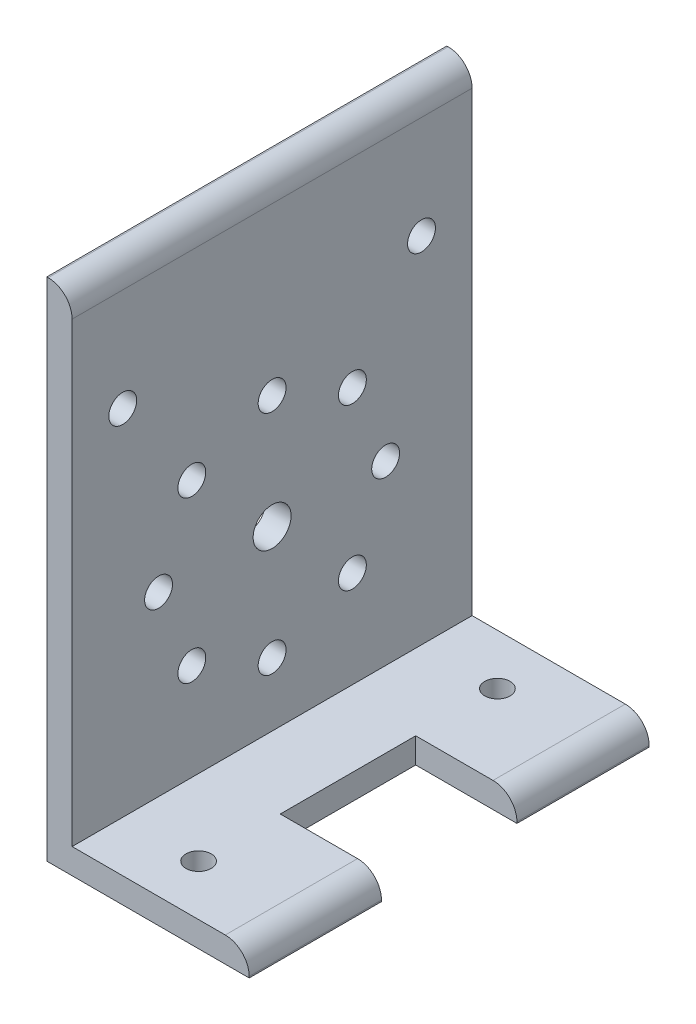
SolidWorks part; units mm, degrees
ref_plane "Front Plane" through (0, 0, 0) normal (0, 0, 1) x (1, 0, 0)
ref_plane "Top Plane" through (0, 0, 0) normal (0, 1, 0) x (1, 0, 0)
ref_plane "Right Plane" through (0, 0, 0) normal (1, 0, 0) x (0, 0, -1)
sketch "Sketch1" plane through (0, 0, 0) normal (0, 0, 1) x (1, 0, 0)
  line L0 (12.35, 6.35) -> (6.35, 6.35)
  line L1 (0, 0) -> (6.35, 0)
  line L2 (0, 0) -> (0, 127)
  line L3 (0, 127) -> (0.35, 127)
  line L4 (6.35, 37.75) -> (6.35, 121)
  line L5 (0, 0) -> (50.8, 0)
  line L6 (0, 0) -> (0, 6.35)
  line L7 (12.35, 6.35) -> (44.8, 6.35)
  line L8 (50.8, 0) -> (50.8, 0.35)
  line L9 (6.35, 6.35) -> (6.35, 37.75)
  arc A0 (44.8, 6.35) -> (50.8, 0.35) centre (44.8, 0.35) cw
  arc A1 (0.35, 127) -> (6.35, 121) centre (0.35, 121) cw
  point P10 (50.8, 6.35)
  point P13 (6.35, 127)
  dimension "D5" = 6
  dimension "D1" = 127
  dimension "D2" = 50.8
  dimension "D3" = 6.35
  dimension "D4" = 6.35
extrude "Boss-Extrude1" add sketch "Sketch1" along normal blind 100.4 contours L7 L4 A1 L3 L2 L1 L5 L8 A0 region at (28.575, 4.9822, 0)
sketch "Sketch2" plane through (0, 0, 0) normal (-1, 0, 0) x (0, 0, 1)
  line L0 (50.2, 0) -> (50.2, 127) construction
  line L1 (100.4, 0) -> (0, 0) construction
  line L2 (100.4, 127) -> (0, 127) construction
  line L3 (100.4, 50.8) -> (0, 50.8) construction
  line L4 (100.4, 0) -> (100.4, 127) construction
  line L5 (0, 0) -> (0, 127) construction
  circle A0 centre (50.2, 50.8) radius 28.5 construction
  circle A9 centre (50.2, 50.8) radius 4.7625
  circle A10 centre (50.2, 79.3) radius 3.5
  circle A18 centre (70.3525, 70.9525) radius 3.5
  circle A19 centre (78.7, 50.8) radius 3.5
  circle A20 centre (70.3525, 30.6475) radius 3.5
  circle A21 centre (50.2, 22.3) radius 3.5
  circle A22 centre (30.0475, 30.6475) radius 3.5
  circle A23 centre (21.7, 50.8) radius 3.5
  circle A24 centre (30.0475, 70.9525) radius 3.5
  dimension "D1" = 57
  dimension "D2" = 8
  dimension "D4" = 9.525
  dimension "D5" = 50.8
extrude "Cut-Extrude1" cut sketch "Sketch2" against normal through all
sketch "Sketch3" plane through (0, 6.35, 0) normal (0, 1, 0) x (1, 0, 0)
  line L0 (25.4, 0) -> (25.4, -100.4) construction
  line L1 (6.35, 0) -> (44.8, 0) construction
  line L2 (6.35, -100.4) -> (44.8, -100.4) construction
  line L3 (0, -100.4) -> (0, 0) construction
  circle A0 centre (25.4, -12.7) radius 3.175
  circle A2 centre (25.4, -87.7) radius 3.175
  dimension "D2" = 6.35
  dimension "D3" = 12.7
  dimension "D5" = 6.35
  dimension "D6" = 12.7
  dimension "D1" = 25.4
extrude "Cut-Extrude2" cut sketch "Sketch3" against normal through all
ref_plane "Width Centerline Plane" through (0, 0, 50.2) normal (0, 0, 1) x (1, 0, 0)
sketch "Sketch4" plane through (0, 6.35, 0) normal (0, 1, 0) x (1, 0, 0)
  line L0 (44.8, 0) -> (44.8, -100.4) construction
  line L5 (50.8, -100.4) -> (50.8, 0) construction
  line L6 (0, -50.2) -> (25.4, -50.2) construction
  line L9 (50.8, -50.2) -> (50.8, -33.2)
  line L10 (50.8, -33.2) -> (25.4, -33.2)
  line L11 (25.4, -50.2) -> (25.4, -33.2)
  line L13 (25.4, -50.2) -> (25.4, -67.2)
  line L14 (25.4, -67.2) -> (50.8, -67.2)
  line L15 (50.8, -50.2) -> (50.8, -67.2)
  point P8 (44.8, -50.2)
  dimension "D1" = 25.4
  dimension "D2" = 17
  dimension "D3" = 17
extrude "Cut-Extrude3" cut sketch "Sketch4" against normal through all
sketch "Sketch5" plane through (6.35, 0, 0) normal (1, 0, 0) x (0, 0, -1)
  line L0 (-50.2, 121) -> (-50.2, 6.35) construction
  line L1 (-100.4, 121) -> (0, 121) construction
  line L3 (-100.4, 6.35) -> (-100.4, 121) construction
  line L4 (-100.4, 6.35) -> (0, 6.35) construction
  circle A0 centre (-87.7, 95.25) radius 3.5
  circle A1 centre (-12.7, 95.25) radius 3.5
  dimension "D1" = 7
  dimension "D2" = 25.75
  dimension "D3" = 12.7
extrude "Cut-Extrude4" cut sketch "Sketch5" against normal blind 10
